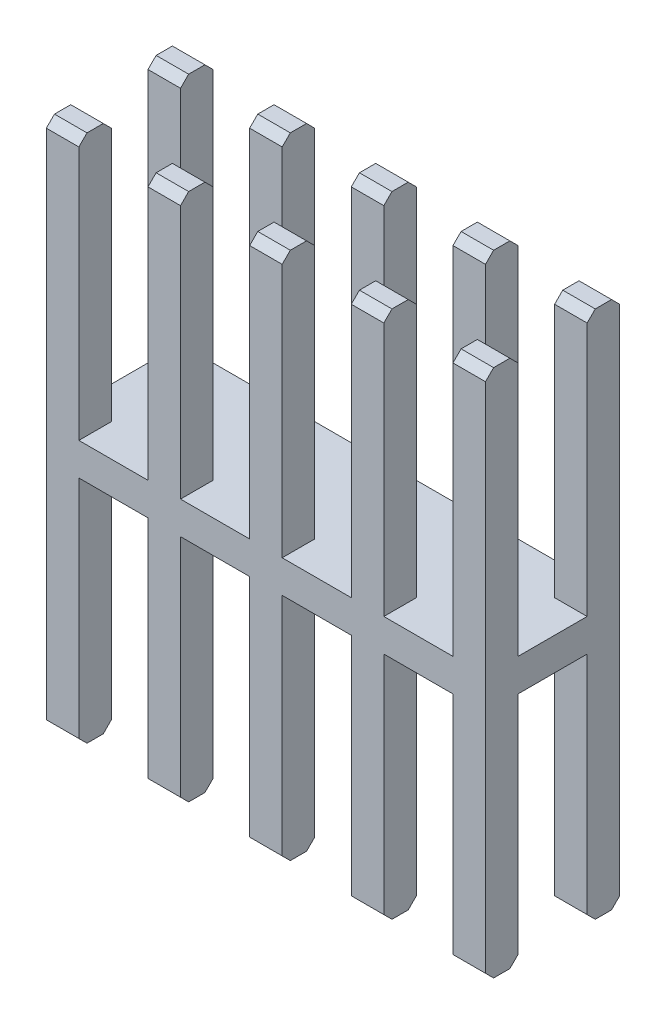
SolidWorks part; units mm, degrees
ref_plane "Front Plane" through (0, 0, 0) normal (0, 0, 1) x (1, 0, 0)
ref_plane "Top Plane" through (0, 0, 0) normal (0, 1, 0) x (1, 0, 0)
ref_plane "Right Plane" through (0, 0, 0) normal (1, 0, 0) x (0, 0, -1)
ref_plane "Plane1" through (0, 0, 0) normal (1, 0, 0) x (0, 0, -1)
sketch "Sketch1" plane through (0, 0, 0) normal (1, 0, 0) x (0, 0, -1)
  line L0 (-0.8382, -1.8034) -> (-0.7366, -1.905)
  line L1 (-0.7366, -1.905) -> (-0.5334, -1.905)
  line L2 (-0.5334, -1.905) -> (-0.4318, -1.8034)
  line L3 (-0.4318, -1.8034) -> (-0.4318, 1.016)
  line L4 (-0.4318, 1.016) -> (0.4318, 1.016)
  line L5 (0.4318, 1.016) -> (0.4318, -1.8034)
  line L6 (0.4318, -1.8034) -> (0.5334, -1.905)
  line L7 (0.5334, -1.905) -> (0.7366, -1.905)
  line L8 (0.7366, -1.905) -> (0.8382, -1.8034)
  line L9 (0.8382, -1.8034) -> (0.8382, 4.5974)
  line L10 (0.8382, 4.5974) -> (0.7366, 4.699)
  line L11 (0.7366, 4.699) -> (0.5334, 4.699)
  line L12 (0.5334, 4.699) -> (0.4318, 4.5974)
  line L13 (0.4318, 4.5974) -> (0.4318, 1.4224)
  line L14 (0.4318, 1.4224) -> (-0.4318, 1.4224)
  line L15 (-0.4318, 1.4224) -> (-0.4318, 4.5974)
  line L16 (-0.4318, 4.5974) -> (-0.5334, 4.699)
  line L17 (-0.5334, 4.699) -> (-0.7366, 4.699)
  line L18 (-0.7366, 4.699) -> (-0.8382, 4.5974)
  line L19 (-0.8382, 4.5974) -> (-0.8382, -1.8034)
extrude "Boss-Extrude1" add sketch "Sketch1" against normal blind 2.7432 and the other way blind 2.7432
ref_plane "Plane2" through (0, 0, 0) normal (0, 0, 1) x (1, 0, 0)
sketch "Sketch2" plane through (0, 0, 0) normal (0, 0, 1) x (1, 0, 0)
  line L0 (-3.6068, -2.413) -> (4.0132, -2.413)
  line L1 (4.0132, -2.413) -> (4.0132, -1.905)
  line L2 (4.0132, -1.905) -> (3.6068, -1.905)
  line L3 (3.6068, -1.905) -> (3.6068, 1.016)
  line L4 (3.6068, 1.016) -> (2.7432, 1.016)
  line L5 (2.7432, 1.016) -> (2.7432, -1.905)
  line L6 (2.7432, -1.905) -> (2.3368, -1.905)
  line L7 (2.3368, -1.905) -> (2.3368, 1.016)
  line L8 (2.3368, 1.016) -> (1.4732, 1.016)
  line L9 (1.4732, 1.016) -> (1.4732, -1.905)
  line L10 (1.4732, -1.905) -> (1.0668, -1.905)
  line L11 (1.0668, -1.905) -> (1.0668, 1.016)
  line L12 (1.0668, 1.016) -> (0.2032, 1.016)
  line L13 (0.2032, 1.016) -> (0.2032, -1.905)
  line L14 (0.2032, -1.905) -> (-0.2032, -1.905)
  line L15 (-0.2032, -1.905) -> (-0.2032, 1.016)
  line L16 (-0.2032, 1.016) -> (-1.0668, 1.016)
  line L17 (-1.0668, 1.016) -> (-1.0668, -1.905)
  line L18 (-1.0668, -1.905) -> (-1.4732, -1.905)
  line L19 (-1.4732, -1.905) -> (-1.4732, 1.016)
  line L20 (-1.4732, 1.016) -> (-2.3368, 1.016)
  line L21 (-2.3368, 1.016) -> (-2.3368, -1.905)
  line L22 (-2.3368, -1.905) -> (-2.7432, -1.905)
  line L23 (-2.7432, -1.905) -> (-2.7432, 1.016)
  line L24 (-2.7432, 1.016) -> (-3.6068, 1.016)
  line L25 (-3.6068, 1.016) -> (-3.6068, -2.413)
extrude "Cut-Extrude1" cut sketch "Sketch2" against normal blind 2.794 and the other way blind 2.794
ref_plane "Plane3" through (0, 0, 0) normal (0, 0, 1) x (1, 0, 0)
sketch "Sketch3" plane through (0, 0, 0) normal (0, 0, 1) x (1, 0, 0)
  line L0 (-3.6068, 5.3594) -> (-3.6068, 1.4224)
  line L1 (-3.6068, 1.4224) -> (-2.7432, 1.4224)
  line L2 (-2.7432, 1.4224) -> (-2.7432, 4.8514)
  line L3 (-2.7432, 4.8514) -> (-2.3368, 4.8514)
  line L4 (-2.3368, 4.8514) -> (-2.3368, 1.4224)
  line L5 (-2.3368, 1.4224) -> (-1.4732, 1.4224)
  line L6 (-1.4732, 1.4224) -> (-1.4732, 4.8514)
  line L7 (-1.4732, 4.8514) -> (-1.0668, 4.8514)
  line L8 (-1.0668, 4.8514) -> (-1.0668, 1.4224)
  line L9 (-1.0668, 1.4224) -> (-0.2032, 1.4224)
  line L10 (-0.2032, 1.4224) -> (-0.2032, 4.8514)
  line L11 (-0.2032, 4.8514) -> (0.2032, 4.8514)
  line L12 (0.2032, 4.8514) -> (0.2032, 1.4224)
  line L13 (0.2032, 1.4224) -> (1.0668, 1.4224)
  line L14 (1.0668, 1.4224) -> (1.0668, 4.8514)
  line L15 (1.0668, 4.8514) -> (1.4732, 4.8514)
  line L16 (1.4732, 4.8514) -> (1.4732, 1.4224)
  line L17 (1.4732, 1.4224) -> (2.3368, 1.4224)
  line L18 (2.3368, 1.4224) -> (2.3368, 4.8514)
  line L19 (2.3368, 4.8514) -> (2.7432, 4.8514)
  line L20 (2.7432, 4.8514) -> (2.7432, 1.4224)
  line L21 (2.7432, 1.4224) -> (3.6068, 1.4224)
  line L22 (3.6068, 1.4224) -> (3.6068, 4.8514)
  line L23 (3.6068, 4.8514) -> (4.0132, 4.8514)
  line L24 (4.0132, 4.8514) -> (4.0132, 5.3594)
  line L25 (4.0132, 5.3594) -> (-3.6068, 5.3594)
extrude "Cut-Extrude2" cut sketch "Sketch3" against normal blind 2.794 and the other way blind 2.794
